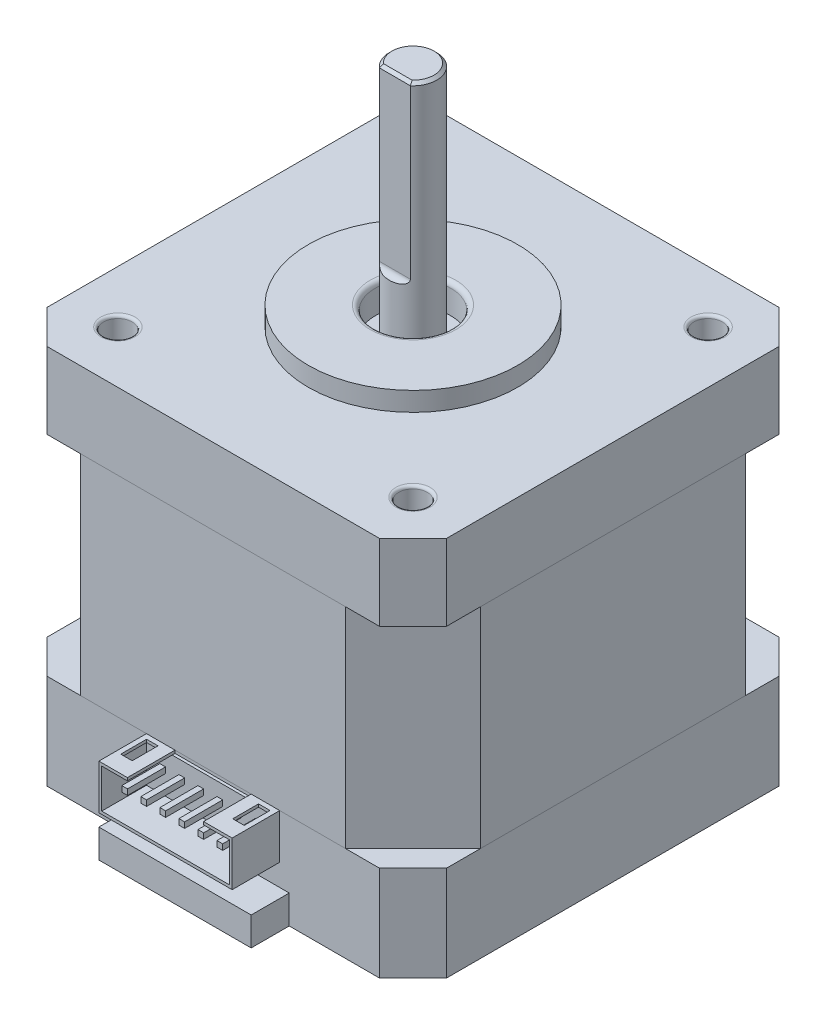
SolidWorks part; units mm, degrees
ref_plane "Front Plane" through (0, 0, 0) normal (0, 0, 1) x (1, 0, 0)
ref_plane "Top Plane" through (0, 0, 0) normal (0, 1, 0) x (1, 0, 0)
ref_plane "Right Plane" through (0, 0, 0) normal (1, 0, 0) x (0, 0, -1)
sketch "Sketch1" plane through (0, 0, 0) normal (0, 1, 0) x (1, 0, 0)
  line L0 (-21, 17.4645) -> (-17.4645, 21)
  line L1 (17.4645, -21) -> (-17.4645, -21)
  line L2 (21, -17.4645) -> (21, 17.4645)
  line L3 (17.4645, 21) -> (-17.4645, 21)
  line L4 (-21, -17.4645) -> (-21, 17.4645)
  line L6 (19.2322, 19.2322) -> (-19.2322, -19.2322) construction
  line L7 (17.4645, -21) -> (21, -17.4645)
  line L8 (-21, 0) -> (21, 0) construction
  line L9 (17.4645, 21) -> (21, 17.4645)
  line L10 (-21, -17.4645) -> (-17.4645, -21)
  point P0 (0, 0)
  point P4 (0, 21)
  dimension "D1" = 42
  dimension "D2" = 42
  dimension "D3" = 5
  dimension "D4" = 45
extrude "bottom" add sketch "Sketch1" along normal blind 10
sketch "Sketch2" plane through (0, 10, 0) normal (0, 1, 0) x (1, 0, 0)
  line L4 (-21, 0) -> (21, 0) construction
  line L5 (-21, 17.4645) -> (-21, -17.4645) construction
  line L6 (21, -17.4645) -> (21, 17.4645) construction
  line L7 (0, 21) -> (0, -21) construction
  line L8 (17.4645, 21) -> (-17.4645, 21) construction
  line L9 (-17.4645, -21) -> (17.4645, -21) construction
  line L10 (-21, 13.9289) -> (-13.9289, 21)
  line L11 (21, 13.9289) -> (13.9289, 21)
  line L16 (-21, -13.9289) -> (-13.9289, -21)
  line L17 (21, -13.9289) -> (13.9289, -21)
  line L18 (-13.9289, 21) -> (13.9289, 21)
  line L19 (21, 13.9289) -> (21, -13.9289)
  line L20 (13.9289, -21) -> (-13.9289, -21)
  line L22 (-21, -13.9289) -> (-21, 13.9289)
  dimension "D1" = 45
  dimension "D2" = 10
extrude "middle" add sketch "Sketch2" along normal blind 22 separate body
sketch "Sketch3" plane through (0, 32, 0) normal (0, 1, 0) x (1, 0, 0)
  line L32 (-21, 17.4645) -> (-21, -17.4645)
  line L33 (-17.4645, 21) -> (-21, 17.4645)
  line L34 (17.4645, 21) -> (-17.4645, 21)
  line L35 (21, 17.4645) -> (17.4645, 21)
  line L36 (21, -17.4645) -> (21, 17.4645)
  line L37 (17.4645, -21) -> (21, -17.4645)
  line L38 (-17.4645, -21) -> (17.4645, -21)
  line L39 (-21, -17.4645) -> (-17.4645, -21)
  line L40 (-21, 17.4645) -> (-21, -17.4645)
  line L41 (-17.4645, 21) -> (-21, 17.4645)
  line L42 (17.4645, 21) -> (-17.4645, 21)
  line L43 (21, 17.4645) -> (17.4645, 21)
  line L44 (21, -17.4645) -> (21, 17.4645)
  line L45 (17.4645, -21) -> (21, -17.4645)
  line L46 (-17.4645, -21) -> (17.4645, -21)
  line L47 (-21, -17.4645) -> (-17.4645, -21)
  dimension "D1" = 0
extrude "top" add sketch "Sketch3" along normal blind 10 separate body
sketch "Sketch4" plane through (0, 0, 21) normal (0, 0, 1) x (1, 0, 0)
  line L0 (-17.4645, 0) -> (17.4645, 0) construction
  line L1 (-8, 0) -> (8, 0)
  line L2 (-8, 0) -> (-8, 3)
  line L3 (-8, 3) -> (8, 3)
  line L4 (8, 0) -> (8, 3)
  point P6 (0, 3)
  dimension "D1" = 16
  dimension "D2" = 3
extrude "JST_extension" add sketch "Sketch4" along normal blind 4
sketch "Sketch5" plane through (0, 42, 0) normal (0, 1, 0) x (1, 0, 0)
  circle A0 centre (0, 0) radius 11
  dimension "D1" = 22
extrude "top trim" cut sketch "Sketch5" against normal blind 2 flip side to cut
sketch "Sketch9" plane through (0, 40, 0) normal (0, 1, 0) x (1, 0, 0)
  line L0 (0, 21) -> (0, 0) construction
  line L1 (17.4645, 21) -> (-17.4645, 21) construction
  line L2 (0, 0) -> (21, 0) construction
  line L3 (21, -17.4645) -> (21, 17.4645) construction
  circle A0 centre (-15.5, 15.5) radius 1.5
  circle A1 centre (15.5, 15.5) radius 1.5
  circle A2 centre (-15.5, -15.5) radius 1.5
  circle A3 centre (15.5, -15.5) radius 1.5
  dimension "D3" = 3
  dimension "D1" = 31
  dimension "D2" = 31
extrude "mount" cut sketch "Sketch9" against normal blind 5
sketch "Sketch6" plane through (0, 42, 0) normal (0, 1, 0) x (1, 0, 0)
  circle A0 centre (0, 0) radius 4
  dimension "D1" = 8
extrude "shaft_recess" cut sketch "Sketch6" against normal blind 3
sketch "Sketch7" plane through (0, 39, 0) normal (0, 1, 0) x (1, 0, 0)
  circle A0 centre (0, 0) radius 2.5
  dimension "D1" = 5
extrude "shaft" add sketch "Sketch7" along normal blind 25 separate body
sketch "Sketch8" plane through (0, 64, 0) normal (0, 1, 0) x (1, 0, 0)
  line L0 (-1.6248, -1.9) -> (1.6248, -1.9)
  circle A0 centre (0, 0) radius 2.5 construction
  arc A1 (-1.6248, -1.9) -> (1.6248, -1.9) centre (0, 0) ccw
  point P5 (0, -2.5)
  dimension "D1" = 0.6
extrude "D_shaft_trim" cut sketch "Sketch8" against normal blind 18.5
chamfer "shaft_top_chamfer" distance 0.3 angle 45 2 edges at (0, 64, -2.5) (0, 64, 1.9)
sketch "Sketch10" plane through (0, 0, 21) normal (0, 0, 1) x (1, 0, 0)
  line L0 (-13.9289, 10) -> (13.9289, 10) construction
  line L1 (7, 5.3) -> (-7, 5.3)
  line L2 (7, 5.3) -> (7, 10)
  line L3 (7, 10) -> (-7, 10)
  line L4 (-7, 5.3) -> (-7, 10)
  line L5 (7, 5.3) -> (-7, 10) construction
  line L6 (7, 10) -> (-7, 5.3) construction
  point P0 (0, 7.65)
  point P7 (0, 0)
  dimension "D1" = 4.7
  dimension "D2" = 14
extrude "JST" add sketch "Sketch10" along normal blind 5 separate body
shell "JST_shell" thickness 0.3 removed face at (0, 7.65, 26)
sketch "Sketch11" plane through (0, 10, 0) normal (0, 1, 0) x (1, 0, 0)
  line L0 (-17.4645, -21) -> (17.4645, -21) construction
  line L1 (4, -26.2916) -> (-4, -26.2916)
  line L2 (4, -26.2916) -> (4, -21)
  line L3 (4, -21) -> (-4, -21)
  line L4 (-4, -26.2916) -> (-4, -21)
  line L5 (4, -26.2916) -> (-4, -21) construction
  line L6 (4, -21) -> (-4, -26.2916) construction
  line L8 (6.4842, -21.5035) -> (5.2791, -21.5035)
  line L9 (6.4842, -21.5035) -> (6.4842, -24.2184)
  line L10 (6.4842, -24.2184) -> (5.2791, -24.2184)
  line L11 (5.2791, -21.5035) -> (5.2791, -24.2184)
  line L12 (0, -25.85) -> (0, 25.85) construction
  line L13 (-6.4842, -24.2184) -> (-5.2791, -24.2184)
  line L14 (-5.2791, -21.5035) -> (-5.2791, -24.2184)
  line L15 (-6.4842, -21.5035) -> (-5.2791, -21.5035)
  line L16 (-6.4842, -21.5035) -> (-6.4842, -24.2184)
  point P0 (0, -23.6458)
  dimension "D1" = 8
extrude "JST_shaper" cut sketch "Sketch11" against normal up to surface (0.3 mm away) up to face at (0, 9.7, 23.65)
sketch "Sketch12" plane through (0, 0, 21.3) normal (0, 0, 1) x (1, 0, 0)
  line L0 (-3.29, 8.2775) -> (-3.29, 7.6775)
  line L1 (-5.29, 8.2775) -> (-4.69, 8.2775)
  line L2 (-5.29, 8.2775) -> (-5.29, 7.6775)
  line L3 (-5.29, 7.6775) -> (-4.69, 7.6775)
  line L4 (-4.69, 8.2775) -> (-4.69, 7.6775)
  line L5 (-5.29, 8.2775) -> (-4.69, 7.6775) construction
  line L6 (-5.29, 7.6775) -> (-4.69, 8.2775) construction
  line L7 (-3.29, 8.2775) -> (-2.69, 8.2775)
  line L8 (-2.69, 8.2775) -> (-2.69, 7.6775)
  line L9 (-3.29, 7.6775) -> (-2.69, 7.6775)
  line L10 (-1.29, 8.2775) -> (-1.29, 7.6775)
  line L11 (-1.29, 8.2775) -> (-0.69, 8.2775)
  line L12 (-0.69, 8.2775) -> (-0.69, 7.6775)
  line L13 (-1.29, 7.6775) -> (-0.69, 7.6775)
  line L14 (0.71, 8.2775) -> (0.71, 7.6775)
  line L15 (0.71, 8.2775) -> (1.31, 8.2775)
  line L16 (1.31, 8.2775) -> (1.31, 7.6775)
  line L17 (0.71, 7.6775) -> (1.31, 7.6775)
  line L18 (2.71, 8.2775) -> (2.71, 7.6775)
  line L19 (2.71, 8.2775) -> (3.31, 8.2775)
  line L20 (3.31, 8.2775) -> (3.31, 7.6775)
  line L21 (2.71, 7.6775) -> (3.31, 7.6775)
  line L22 (4.71, 8.2775) -> (4.71, 7.6775)
  line L23 (4.71, 8.2775) -> (5.31, 8.2775)
  line L24 (5.31, 8.2775) -> (5.31, 7.6775)
  line L25 (4.71, 7.6775) -> (5.31, 7.6775)
  line L28 (-6.7, 9.7) -> (-6.7, 5.6) construction
  point P0 (-4.99, 7.9775)
  point P5 (0, 0)
  dimension "D1" = 0.6
  dimension "D3" = 1.71
  dimension "D2" = 6
extrude "JST_pins" add sketch "Sketch12" along normal blind 4 separate body
fillet "Fillet2" radius 0.5 1 edges at (0, 42, 4)
fillet "Fillet3" radius 0.3 4 edges at (-15.5, 40, 14) (-15.5, 40, -14) (15.5, 40, -17) (15.5, 40, 17)
fillet "Fillet4" radius 0.6 1 edges at (0, 45.5, 1.9)
